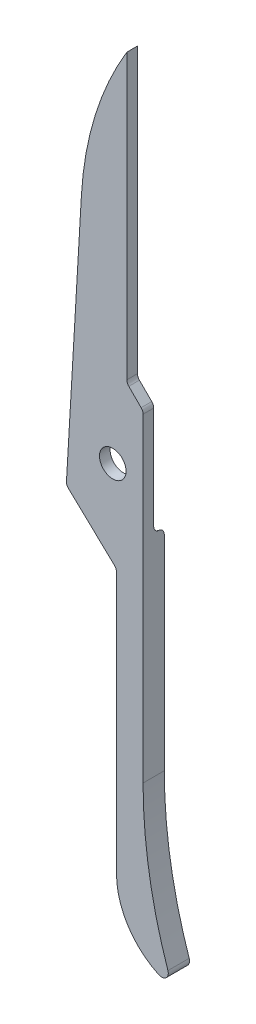
SolidWorks part; units mm, degrees
ref_plane "Płaszczyzna przednia" through (0, 0, 0) normal (0, 0, 1) x (1, 0, 0)
ref_plane "Płaszczyzna górna" through (0, 0, 0) normal (0, 1, 0) x (1, 0, 0)
ref_plane "Płaszczyzna prawa" through (0, 0, 0) normal (1, 0, 0) x (0, 0, -1)
sketch "Sketch1" plane through (0, 0, 0) normal (0, 0, 1) x (1, 0, 0)
  line L0 (3.78, 5.349) -> (3.78, 25.2417)
  line L1 (0, 0) -> (8, 0) construction
  line L2 (0, 0) -> (0, 59.31) construction
  line L3 (0, 59.31) -> (8, 59.31) construction
  line L4 (8, 0) -> (8, 59.31) construction
  line L5 (3.78, 25.2417) -> (0, 28.81)
  line L7 (4.56, 59.31) -> (4.56, 37.74)
  line L8 (4.56, 37.74) -> (5.78, 36.52)
  line L9 (5.78, 36.52) -> (5.78, 12.2667)
  line L10 (0, 28.81) -> (1.1407, 48.2979)
  arc A2 (5.78, 12.2667) -> (8, 0) centre (40.78, 12.2667) ccw
  arc A3 (1.1407, 48.2979) -> (4.56, 59.31) centre (25.0997, 46.8955) cw
  arc A4 (3.78, 5.349) -> (8, 0) centre (9.28, 5.349) ccw
  point P5 (4.56, 59.31)
  point P6 (0, 28.81)
  dimension "D7" = 130
  dimension "D6" = 24
  dimension "D12" = 5.5
  dimension "D13" = 35
  dimension "D1" = 8
  dimension "D2" = 59.31
  dimension "D3" = 4.56
  dimension "D4" = 28.81
  dimension "D5" = 133.35
  dimension "D8" = 21.57
  dimension "D9" = 45
  dimension "D10" = 2.22
  dimension "D11" = 2
extrude "Boss-Extrude1" add sketch "Sketch1" along normal blind 1.6
sketch "Sketch2" plane through (0, 0, 1.6) normal (0, 0, 1) x (1, 0, 0)
  circle A0 centre (3.5, 31.95) radius 1
  point P2 (0, 0)
  point P4 (0, 0)
  point P6 (1.2508, 32.4532)
  dimension "D1" = 2
  dimension "D2" = 3.14
  dimension "D3" = 3.5
extrude "Cut-Extrude1" cut sketch "Sketch2" against normal through all
fillet "Fillet1" radius 0.5 5 edges at (4.56, 37.74, 0.8) (5.78, 36.52, 0.8) (8, 0, 0.8) (3.78, 25.2417, 0.8) (0, 28.81, 0.8)
sketch "Sketch8" plane through (0, 0, 0) normal (0, 0, -1) x (-1, 0, 0)
  line L0 (-2.9438, 26.0311) -> (11.5504, 26.0311)
  line L1 (-0.1695, 28.65) -> (-3.6232, 25.3897) construction
  line L2 (11.5504, 26.0311) -> (11.5504, 65.3146)
  line L3 (11.5504, 65.3146) -> (-14.375, 65.3146)
  line L4 (-14.375, 65.3146) -> (-14.375, 34.53)
  line L5 (-14.375, 34.53) -> (-2.9438, 26.0311)
  dimension "D1" = 143.37
extrude "Cut-Extrude3" cut sketch "Sketch8" against normal blind 0.8
fillet "Fillet2" radius 0.4 2 edges at (4.3619, 27.0854, 0.8) (4.3619, 27.0854, 0)
